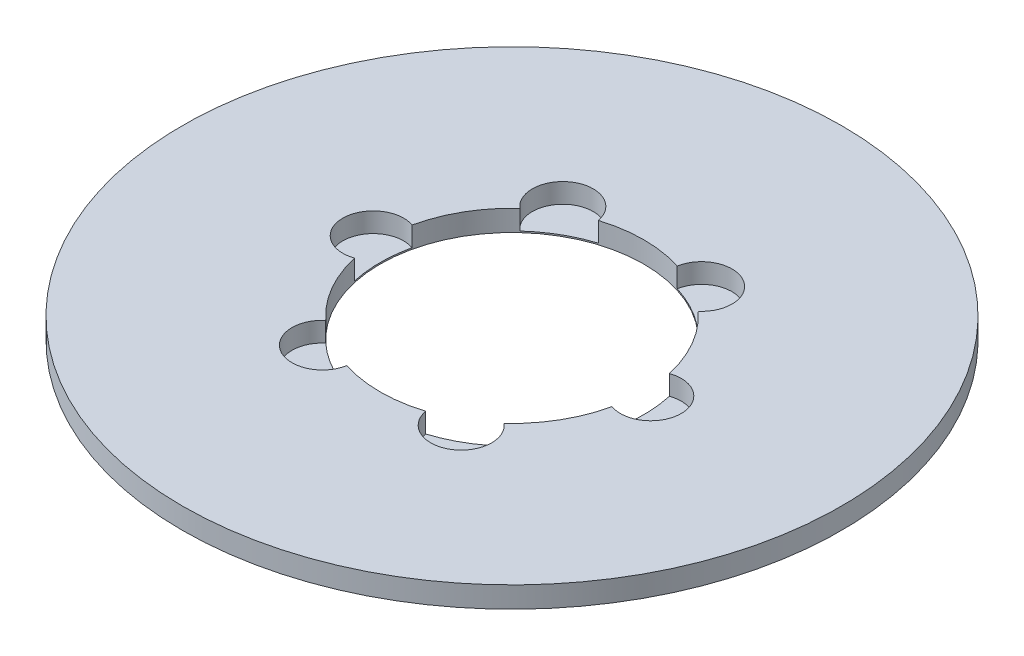
SolidWorks part; units mm, degrees
ref_plane "Front Plane" through (0, 0, 0) normal (0, 0, 1) x (1, 0, 0)
ref_plane "Top Plane" through (0, 0, 0) normal (0, 1, 0) x (1, 0, 0)
ref_plane "Right Plane" through (0, 0, 0) normal (1, 0, 0) x (0, 0, -1)
sketch "Sketch1" plane through (0, 0, 0) normal (0, 1, 0) x (1, 0, 0)
  circle A0 centre (0, 0) radius 62.5
  dimension "FLANGE_OD" = 125
extrude "Boss-Extrude1" add sketch "Sketch1" along normal blind 4
sketch "Sketch2" plane through (0, 0, 0) normal (0, 1, 0) x (1, 0, 0)
  circle A0 centre (0, 0) radius 25
  dimension "BORE_D" = 50
extrude "Cut-Extrude1" cut sketch "Sketch2" along normal through all
sketch "Sketch3" plane through (0, 4, 0) normal (0, 1, 0) x (1, 0, 0)
  circle A0 centre (0, 0) radius 26.3178 construction
  circle A1 centre (-26.3178, 0) radius 5.7756
  dimension "BOLT_D" = 11.5512
  dimension "BOLT_PCD" = 52.6356
extrude "Cut-Extrude2" cut sketch "Sketch3" against normal blind 3.7352
pattern_circular "CirPattern1" count 6 over 360 about axis through (0, 0, 0) along (0, 1, 0) of "Cut-Extrude2"
